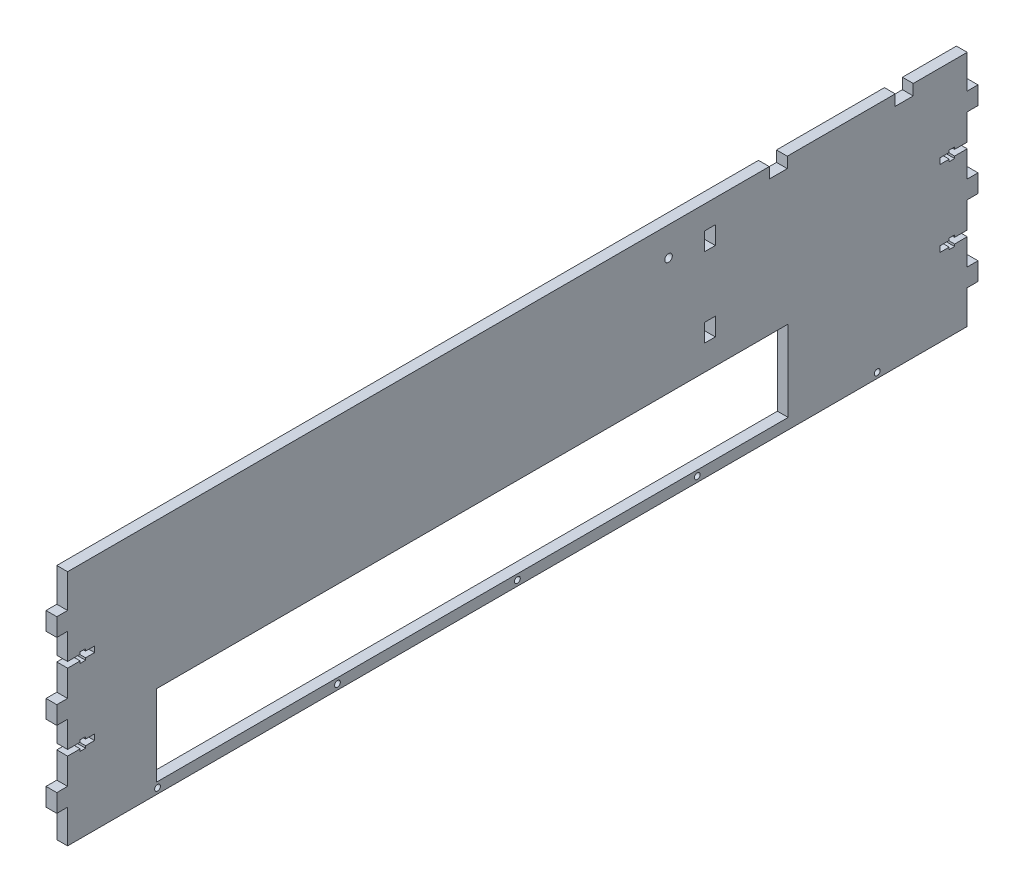
SolidWorks part; units mm, degrees
ref_plane "Front Plane" through (0, 0, 0) normal (0, 0, 1) x (1, 0, 0)
ref_plane "Top Plane" through (0, 0, 0) normal (0, 1, 0) x (1, 0, 0)
ref_plane "Right Plane" through (0, 0, 0) normal (1, 0, 0) x (0, 0, -1)
sketch "Sketch1" plane through (0, 0, 0) normal (1, 0, 0) x (0, 0, -1)
  line L1 (-250, -66) -> (250, -66)
  line L2 (-250, -66) -> (-250, 66)
  line L3 (-250, 66) -> (250, 66)
  line L4 (250, -66) -> (250, 66)
  line L5 (-250, -66) -> (250, 66) construction
  line L6 (-250, 66) -> (250, -66) construction
  point P0 (0, 0)
  dimension "D1" = 132
  dimension "D2" = 500
extrude "Boss-Extrude1" add sketch "Sketch1" along normal blind 6
sketch "Sketch4" plane through (0, 0, 250) normal (0, 0, 1) x (1, 0, 0)
  line L0 (0, 66) -> (0, -66) construction
  line L1 (0, 47.3321) -> (6, 47.3321)
  line L2 (0, 47.3321) -> (0, 37.3321)
  line L3 (0, 37.3321) -> (6, 37.3321)
  line L4 (6, 47.3321) -> (6, 37.3321)
  line L5 (6, 66) -> (6, -66) construction
  line L6 (0, 37.3321) -> (6, 37.3321) construction
  line L7 (0, -66) -> (0, 66) construction
  line L8 (6, 47.3321) -> (0, 47.3321) construction
  line L9 (0, -5) -> (6, -5) construction
  line L10 (0, -5) -> (6, -5)
  line L11 (0, -5) -> (0, 5)
  line L12 (0, 5) -> (6, 5)
  line L13 (6, -5) -> (6, 5)
  line L14 (6, -66) -> (6, 66) construction
  line L15 (6, 5) -> (0, 5) construction
  line L16 (6, -37.3321) -> (0, -37.3321) construction
  line L17 (0, -47.3321) -> (6, -47.3321)
  line L18 (0, -47.3321) -> (0, -37.3321)
  line L19 (0, -37.3321) -> (6, -37.3321)
  line L20 (6, -47.3321) -> (6, -37.3321)
  line L21 (0, -47.3321) -> (6, -47.3321) construction
extrude "Boss-Extrude2" add sketch "Sketch4" along normal blind 6
sketch "Sketch5" plane through (0, 0, 0) normal (-1, 0, 0) x (0, 0, 1)
  line L0 (250, 37.3321) -> (250, 5) construction
  line L1 (250, 5) -> (250, -5) construction
  line L2 (250, -5) -> (250, -37.3321) construction
  line L3 (250, 21.1661) -> (235, 21.1661) construction
  line L4 (240, -23.9661) -> (243, -18.3661) construction
  line L5 (250, 22.7661) -> (235, 22.7661)
  line L6 (240, -18.3661) -> (243, -23.9661) construction
  line L7 (250, 19.5661) -> (235, 19.5661)
  line L8 (250, -21.1661) -> (235, -21.1661) construction
  line L9 (250, 22.7661) -> (250, 19.5661)
  line L10 (235, 22.7661) -> (235, 19.5661)
  line L11 (243, -18.3661) -> (243, -23.9661)
  line L12 (240, -23.9661) -> (243, -23.9661)
  line L13 (250, 0) -> (222.8268, 0) construction
  line L14 (240, 18.3661) -> (243, 18.3661)
  line L15 (240, 18.3661) -> (240, 23.9661)
  line L16 (240, 23.9661) -> (243, 23.9661)
  line L17 (243, 18.3661) -> (243, 23.9661)
  line L18 (240, 18.3661) -> (243, 23.9661) construction
  line L19 (240, 23.9661) -> (243, 18.3661) construction
  line L20 (240, -18.3661) -> (240, -23.9661)
  line L21 (240, -18.3661) -> (243, -18.3661)
  line L22 (235, -22.7661) -> (235, -19.5661)
  line L23 (250, -22.7661) -> (250, -19.5661)
  line L24 (250, -19.5661) -> (235, -19.5661)
  line L25 (250, -22.7661) -> (235, -22.7661)
  point P20 (241.5, 21.1661)
  point P29 (241.5, -21.1661)
  dimension "D3" = 15
  dimension "D4" = 7
  dimension "D5" = 3
  dimension "D6" = 5.6
  dimension "D1" = 1.6
  dimension "D2" = 1.6
extrude "Cut-Extrude3" cut sketch "Sketch5" against normal up to next contours L17 L7 L9 L5 | L7 L17 L5 L15 | L5 L17 L16 L15 | L14 L17 L7 L15 | L7 L15 L5 L10 | L25 L23 L24 L11 | L25 L11 L24 L20 | L24 L11 L21 L20 | L11 L25 L20 L12 | L25 L20 L24 L22 region at (0, 21.1661, 246.5) region at (0, 21.1661, 241.5) region at (0, 23.3661, 241.5) region at (0, 21.1661, 237.5) region at (0, 18.9661, 241.5) region at (0, -18.9661, 241.5) region at (0, -21.1661, 246.5) region at (0, -21.1661, 241.5) region at (0, -23.3661, 241.5) region at (0, -21.1661, 237.5)
sketch "Sketch6" plane through (0, 0, -250) normal (0, 0, -1) x (-1, 0, 0)
  line L0 (0, 47.3321) -> (0, 37.3321) construction
  line L1 (0, 37.3321) -> (-6, 37.3321) construction
  line L2 (-6, 37.3321) -> (-6, 47.3321) construction
  line L3 (-6, 47.3321) -> (0, 47.3321) construction
  line L4 (0, 5) -> (0, -5) construction
  line L5 (0, -5) -> (-6, -5) construction
  line L6 (-6, -5) -> (-6, 5) construction
  line L7 (-6, 5) -> (0, 5) construction
  line L8 (0, -37.3321) -> (0, -47.3321) construction
  line L9 (0, -47.3321) -> (-6, -47.3321) construction
  line L10 (-6, -47.3321) -> (-6, -37.3321) construction
  line L11 (-6, -37.3321) -> (0, -37.3321) construction
  line L12 (0, 47.3321) -> (0, 37.3321)
  line L13 (0, 37.3321) -> (-6, 37.3321)
  line L14 (-6, 37.3321) -> (-6, 47.3321)
  line L15 (-6, 47.3321) -> (0, 47.3321)
  line L16 (0, 5) -> (0, -5)
  line L17 (0, -5) -> (-6, -5)
  line L18 (-6, -5) -> (-6, 5)
  line L19 (-6, 5) -> (0, 5)
  line L20 (0, -37.3321) -> (0, -47.3321)
  line L21 (0, -47.3321) -> (-6, -47.3321)
  line L22 (-6, -47.3321) -> (-6, -37.3321)
  line L23 (-6, -37.3321) -> (0, -37.3321)
extrude "Boss-Extrude3" add sketch "Sketch6" along normal blind 6
sketch "Sketch7" plane through (0, 0, 0) normal (-1, 0, 0) x (0, 0, 1)
  line L0 (0, 0) -> (0, -63.2146) construction
  line L1 (240, 22.7661) -> (240, 23.9661) construction
  line L2 (240, 22.7661) -> (235, 22.7661) construction
  line L3 (235, 22.7661) -> (235, 19.5661) construction
  line L4 (240, 19.5661) -> (235, 19.5661) construction
  line L5 (240, 18.3661) -> (240, 19.5661) construction
  line L6 (240, 18.3661) -> (243, 18.3661) construction
  line L7 (243, 18.3661) -> (243, 19.5661) construction
  line L8 (250, 19.5661) -> (243, 19.5661) construction
  line L9 (250, 22.7661) -> (243, 22.7661) construction
  line L10 (240, 23.9661) -> (243, 23.9661) construction
  line L11 (243, 22.7661) -> (243, 23.9661) construction
  line L12 (240, 22.7661) -> (235, 22.7661) construction
  line L13 (235, 22.7661) -> (235, 19.5661) construction
  line L14 (240, 19.5661) -> (235, 19.5661) construction
  line L15 (240, 18.3661) -> (240, 19.5661) construction
  line L16 (240, 18.3661) -> (243, 18.3661) construction
  line L17 (243, 18.3661) -> (243, 19.5661) construction
  line L18 (250, 19.5661) -> (243, 19.5661) construction
  line L19 (250, 22.7661) -> (243, 22.7661) construction
  line L20 (240, 23.9661) -> (243, 23.9661) construction
  line L21 (243, 22.7661) -> (243, 23.9661) construction
  line L22 (240, 22.7661) -> (240, 23.9661) construction
  line L23 (250, -19.5661) -> (243, -19.5661) construction
  line L24 (240, -18.3661) -> (243, -18.3661) construction
  line L25 (243, -18.3661) -> (243, -19.5661) construction
  line L26 (240, -18.3661) -> (240, -19.5661) construction
  line L27 (240, -19.5661) -> (235, -19.5661) construction
  line L28 (235, -22.7661) -> (235, -19.5661) construction
  line L29 (240, -22.7661) -> (235, -22.7661) construction
  line L30 (240, -22.7661) -> (240, -23.9661) construction
  line L31 (240, -23.9661) -> (243, -23.9661) construction
  line L32 (243, -22.7661) -> (243, -23.9661) construction
  line L33 (250, -22.7661) -> (243, -22.7661) construction
  line L34 (250, -19.5661) -> (243, -19.5661) construction
  line L35 (240, -18.3661) -> (243, -18.3661) construction
  line L36 (243, -18.3661) -> (243, -19.5661) construction
  line L37 (240, -18.3661) -> (240, -19.5661) construction
  line L38 (240, -19.5661) -> (235, -19.5661) construction
  line L39 (235, -22.7661) -> (235, -19.5661) construction
  line L40 (240, -22.7661) -> (235, -22.7661) construction
  line L41 (240, -22.7661) -> (240, -23.9661) construction
  line L42 (240, -23.9661) -> (243, -23.9661) construction
  line L43 (243, -22.7661) -> (243, -23.9661) construction
  line L44 (250, -22.7661) -> (243, -22.7661) construction
  line L45 (250, 22.7661) -> (250, 19.5661) construction
  line L46 (250, -19.5661) -> (250, -22.7661) construction
  line L47 (-250, -19.5661) -> (-250, -22.7661)
  line L48 (-250, 22.7661) -> (-250, 19.5661)
  line L49 (-250, -22.7661) -> (-243, -22.7661)
  line L50 (-243, -22.7661) -> (-243, -23.9661)
  line L51 (-240, -23.9661) -> (-243, -23.9661)
  line L52 (-240, -22.7661) -> (-240, -23.9661)
  line L53 (-240, -22.7661) -> (-235, -22.7661)
  line L54 (-235, -22.7661) -> (-235, -19.5661)
  line L55 (-240, -19.5661) -> (-235, -19.5661)
  line L56 (-240, -18.3661) -> (-240, -19.5661)
  line L57 (-243, -18.3661) -> (-243, -19.5661)
  line L58 (-240, -18.3661) -> (-243, -18.3661)
  line L59 (-250, -19.5661) -> (-243, -19.5661)
  line L60 (-240, 22.7661) -> (-240, 23.9661)
  line L61 (-243, 22.7661) -> (-243, 23.9661)
  line L62 (-240, 23.9661) -> (-243, 23.9661)
  line L63 (-250, 22.7661) -> (-243, 22.7661)
  line L64 (-250, 19.5661) -> (-243, 19.5661)
  line L65 (-243, 18.3661) -> (-243, 19.5661)
  line L66 (-240, 18.3661) -> (-243, 18.3661)
  line L67 (-240, 18.3661) -> (-240, 19.5661)
  line L68 (-240, 19.5661) -> (-235, 19.5661)
  line L69 (-235, 22.7661) -> (-235, 19.5661)
  line L70 (-240, 22.7661) -> (-235, 22.7661)
extrude "Cut-Extrude4" cut sketch "Sketch7" against normal up to next
sketch "Sketch8" plane through (0, 0, 0) normal (-1, 0, 0) x (0, 0, 1)
  line L0 (200, -15.55) -> (-150, -15.55) construction
  line L1 (200, -15.55) -> (-150, -15.55) construction
  line L2 (200, -15.55) -> (200, -60) construction
  line L3 (200, -15.55) -> (200, -60) construction
  line L186 (-150, -15.55) -> (-150, -60) construction
  line L187 (-150, -60) -> (200, -60) construction
  line L188 (200.5, -15.05) -> (200.5, -60)
  line L189 (200.5, -15.05) -> (-150.5, -15.05)
  line L190 (-150.5, -15.05) -> (-150.5, -60)
  line L191 (-150.5, -60) -> (200.5, -60)
  dimension "D1" = 0.5
extrude "Cut-Extrude5" cut sketch "Sketch8" against normal up to next
sketch "Sketch10" plane through (6, 0, 0) normal (1, 0, 0) x (0, 0, -1)
  line L0 (0, 0) -> (0, -66) construction
  line L1 (-250, -66) -> (250, -66) construction
  line L2 (0, -63) -> (250, -63) construction
  line L3 (250, -66) -> (250, -47.3321) construction
  circle A0 centre (0, -63) radius 1.6
  circle A1 centre (100, -63) radius 1.6
  circle A2 centre (200, -63) radius 1.6
  circle A3 centre (-100, -63) radius 1.6
  circle A4 centre (-200, -63) radius 1.6
  dimension "D2" = 3.2
  dimension "D1" = 3
  dimension "D3" = 100
  dimension "D4" = 100
extrude "Cut-Extrude7" cut sketch "Sketch10" against normal up to next
sketch "Sketch11" plane through (6, 0, 0) normal (1, 0, 0) x (0, 0, -1)
  line L0 (110, 43) -> (110, 53) construction
  line L1 (110, 53) -> (104, 53) construction
  line L2 (104, 53) -> (104, 43) construction
  line L3 (104, 43) -> (110, 43) construction
  line L4 (110, -1) -> (110, 9) construction
  line L5 (110, 9) -> (104, 9) construction
  line L6 (104, 9) -> (104, -1) construction
  line L7 (104, -1) -> (110, -1) construction
  line L8 (110, 43) -> (110, 53)
  line L9 (110, 53) -> (104, 53)
  line L10 (104, 53) -> (104, 43)
  line L11 (104, 43) -> (110, 43)
  line L12 (110, -1) -> (110, 9)
  line L13 (110, 9) -> (104, 9)
  line L14 (104, 9) -> (104, -1)
  line L15 (104, -1) -> (110, -1)
extrude "Cut-Extrude8" cut sketch "Sketch11" against normal up to next
sketch "Sketch12" plane through (0, 0, 0) normal (-1, 0, 0) x (0, 0, 1)
  line L0 (-104, 53) -> (-104, 43) construction
  line L1 (-250, 66) -> (250, 66) construction
  circle A0 centre (-84, 50) radius 2.1
  dimension "D1" = 20
  dimension "D3" = 4.2
  dimension "D2" = 16
extrude "Cut-Extrude9" cut sketch "Sketch12" against normal up to next
sketch "Sketch13" plane through (0, 66, 0) normal (0, 1, 0) x (1, 0, 0)
  line L0 (6, 250) -> (6, -250) construction
  line L1 (0, 210) -> (6, 210)
  line L2 (0, 210) -> (0, 220)
  line L3 (0, 220) -> (6, 220)
  line L4 (6, 210) -> (6, 220)
  line L5 (0, 210) -> (6, 220) construction
  line L6 (0, 220) -> (6, 210) construction
  line L7 (6, 220) -> (0, 220) construction
  line L8 (6, 150) -> (0, 150) construction
  line L9 (0, 140) -> (6, 140)
  line L10 (0, 140) -> (0, 150)
  line L11 (0, 150) -> (6, 150)
  line L12 (6, 140) -> (6, 150)
  line L13 (0, 140) -> (6, 150) construction
  line L14 (0, 150) -> (6, 140) construction
  point P0 (3, 215)
  point P10 (3, 145)
extrude "Cut-Extrude10" cut sketch "Sketch13" against normal blind 6
